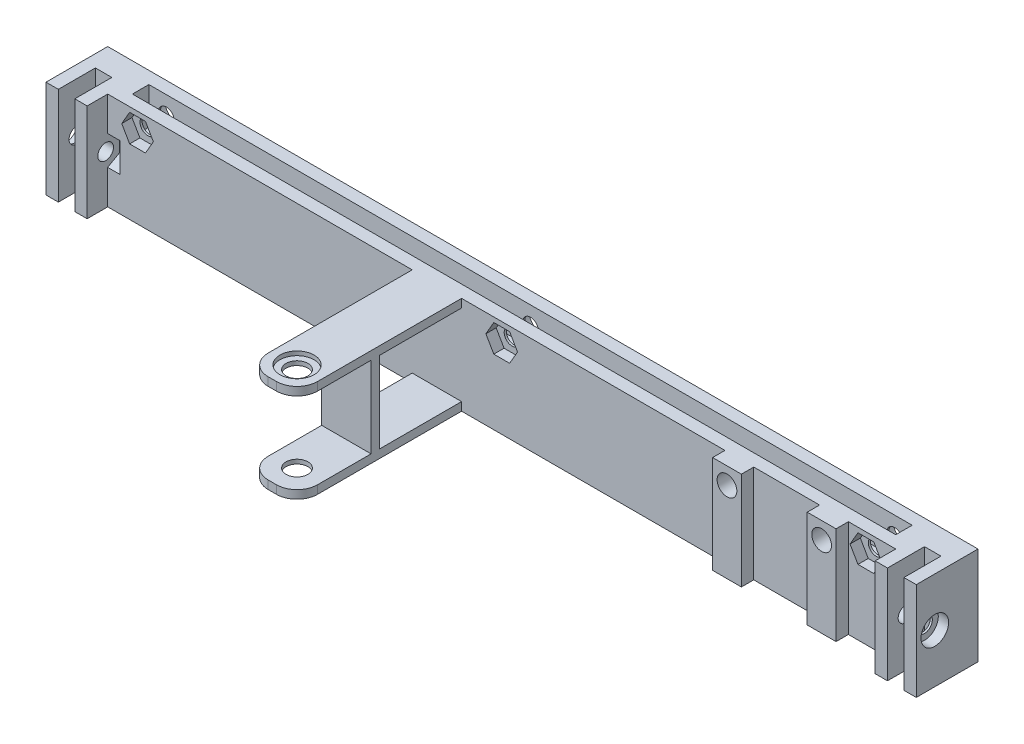
SolidWorks part; units mm, degrees
ref_plane "Front Plane" through (0, 0, 0) normal (1, 0, 0) x (0, 1, 0)
ref_plane "Top Plane" through (0, 0, 0) normal (0, 0, 1) x (0, 1, 0)
ref_plane "Right Plane" through (0, 0, 0) normal (0, 1, 0) x (-1, 0, 0)
sketch "Sketch2" plane through (0, 0, 0) normal (0, 0, 1) x (0, 1, 0)
  line L1 (-71.25, 0) -> (-95, 0)
  line L2 (-71.25, 0) -> (-71.25, 12)
  line L3 (-71.25, 12) -> (-95, 12)
  line L4 (-95, 0) -> (-95, 12)
extrude "Boss-Extrude1" add sketch "Sketch2" along normal blind 10
sketch "Sketch3" plane through (0, 0, 10) normal (0, 0, 1) x (1, 0, 0)
  line L1 (-12, -71.25) -> (0, -71.25)
  line L2 (-12, -71.25) -> (-12, -73.275)
  line L3 (-12, -73.275) -> (0, -73.275)
  line L4 (0, -71.25) -> (0, -73.275)
  line L6 (-12, -73.275) -> (0, -73.275) construction
  dimension "D1" = 2.025
extrude "Boss-Extrude2" add sketch "Sketch3" along normal blind 40
fillet "Fillet1" radius 5 2 edges at (0, -72.2625, 50) (-12, -72.2625, 50)
ref_plane "Plane1" through (0, -83.125, 0) normal (0, 1, 0) x (1, 0, 0)
mirror "Mirror1" about plane through (0, -83.125, 0) normal (0, 1, 0) of "Fillet1", "Boss-Extrude2"
sketch "Sketch5" plane through (0, -95, 0) normal (0, -1, 0) x (1, 0, 0)
  line L1 (-6, 50) -> (-12, 50)
  line L2 (-6, 50) -> (-6, 44)
  line L3 (-6, 44) -> (-12, 44)
  line L4 (-12, 50) -> (-12, 44)
  line L5 (-5, 50) -> (-7, 50) construction
  line L6 (-12, 45) -> (-12, 0) construction
  circle A0 centre (-6, 44) radius 2.65
  dimension "D1" = 6
extrude "Cut-Extrude1" cut sketch "Sketch5" against normal through all contours A0
sketch "Sketch6" plane through (0, -95, 0) normal (0, -1, 0) x (1, 0, 0)
  line L1 (-6, 50) -> (-12, 50)
  line L2 (-6, 50) -> (-6, 44)
  line L3 (-6, 44) -> (-12, 44)
  line L4 (-12, 50) -> (-12, 44)
  line L6 (-5, 50) -> (-7, 50) construction
  line L7 (-12, 45) -> (-12, 0) construction
  circle A0 centre (-6, 44) radius 4.15
  dimension "D1" = 6
extrude "Cut-Extrude2" cut sketch "Sketch6" against normal blind 1 contours A0
mirror "Mirror2" about plane through (0, -83.125, 0) normal (0, 1, 0) of "Cut-Extrude2"
sketch "Sketch7" plane through (0, 0, 0) normal (0, 0, -1) x (1, 0, 0)
  line L1 (-6, 95) -> (-96, 95)
  line L2 (-6, 95) -> (-6, 71.25)
  line L3 (-6, 71.25) -> (-96, 71.25)
  line L4 (-96, 95) -> (-96, 71.25)
  line L5 (-6, 95) -> (115.5, 95)
  line L6 (-6, 95) -> (-6, 71.25)
  line L7 (-6, 71.25) -> (115.5, 71.25)
  line L8 (115.5, 95) -> (115.5, 71.25)
  line L10 (-12, 95) -> (0, 95) construction
  line L11 (0, 71.25) -> (-12, 71.25) construction
  line M20 (0, 71.25) -> (0, 95)
  line M22 (-12, 95) -> (-12, 71.25)
  dimension "D1" = 90
  dimension "D2" = 121.5
extrude "Boss-Extrude3" add sketch "Sketch7" against normal blind 10 contours L1 L4 L3 M22 | L8 L5 L7 M20 region at (-54, -83.125, 0) region at (57.75, -83.125, 0)
sketch "Sketch8" plane through (0, 0, 10) normal (0, 0, 1) x (1, 0, 0)
  line L1 (115.5, -71.25) -> (105.5, -71.25)
  line L2 (115.5, -71.25) -> (115.5, -95)
  line L3 (115.5, -95) -> (105.5, -95)
  line L4 (105.5, -71.25) -> (105.5, -95)
  line L6 (-96, -71.25) -> (-86, -71.25)
  line L7 (-96, -71.25) -> (-96, -95)
  line L8 (-96, -95) -> (-86, -95)
  line L9 (-86, -71.25) -> (-86, -95)
  dimension "D1" = 10
  dimension "D2" = 10
extrude "Boss-Extrude4" add sketch "Sketch8" along normal blind 5
sketch "Sketch10" plane through (-12, 0, 0) normal (-1, 0, 0) x (0, -1, 0)
  line L0 (95, 45) -> (95, 10) construction
  line L1 (71.25, 10) -> (95, 10)
  line L2 (71.25, 10) -> (71.25, 12)
  line L3 (71.25, 12) -> (95, 12)
  line L4 (95, 10) -> (95, 12)
  dimension "D1" = 2
extrude "Boss-Extrude5" [suppressed] add sketch "Sketch10" along normal blind 24
sketch "Sketch18" plane through (0, -71.25, 0) normal (0, 1, 0) x (-1, 0, 0)
  line L1 (0, 10) -> (12, 10)
  line L2 (0, 10) -> (0, 30)
  line L3 (0, 30) -> (12, 30)
  line L4 (12, 10) -> (12, 30)
  line L5 (12, 45) -> (12, 10) construction
  line L6 (0, 30) -> (12, 30)
  line L7 (0, 30) -> (0, 32)
  line L8 (0, 32) -> (12, 32)
  line L9 (12, 30) -> (12, 32)
  dimension "D1" = 20
  dimension "D2" = 2
extrude "Boss-Extrude7" add sketch "Sketch18" against normal through all contours L7 L6 L9 L8
sketch "Sketch11" plane through (0, -71.25, 0) normal (0, 1, 0) x (-1, 0, 0)
  line L1 (86, 0) -> (-105.5, 0)
  line L2 (86, 0) -> (86, 10)
  line L3 (86, 10) -> (-105.5, 10)
  line L4 (-105.5, 0) -> (-105.5, 10)
  line L5 (83, 7) -> (-102.5, 7)
  line L6 (-102.5, 3) -> (-102.5, 7)
  line L7 (83, 3) -> (-102.5, 3)
  line L8 (83, 3) -> (83, 7)
  line L12 (96, 0) -> (86, 0)
  line L13 (96, 0) -> (96, 10)
  line L14 (96, 10) -> (86, 10)
  line L15 (86, 0) -> (86, 10)
extrude "Cut-Extrude3" cut sketch "Sketch11" against normal blind 9 contours L7 L8 L5 L6 region at (9.75, -71.25, 5)
mirror "Mirror3" about plane through (0, -83.125, 0) normal (0, 1, 0) of "Cut-Extrude3"
sketch "Sketch12" plane through (0, 0, 10) normal (0, 0, 1) x (1, 0, 0)
  line L1 (-86, -71.25) -> (-78.75, -71.25)
  line L2 (-86, -71.25) -> (-86, -75.75)
  line L3 (-86, -75.75) -> (-78.75, -75.75)
  line L4 (-78.75, -71.25) -> (-78.75, -75.75)
  circle A0 centre (-78.75, -75.75) radius 1.9
  circle A1 centre (-78.75, -75.75) radius 3.15
  dimension "D3" = 3.8
  dimension "D4" = 6.3
  dimension "D1" = 7.25
  dimension "D2" = 4.5
extrude "Cut-Extrude4" cut sketch "Sketch12" against normal through all and the other way through all contours A0
sketch "Sketch15" plane through (0, 0, 0) normal (0, 0, 1) x (1, 0, 0)
  circle A0 centre (-78.75, -75.75) radius 3.35
  dimension "D1" = 6.7
extrude "Cut-Extrude5" cut sketch "Sketch15" along normal blind 2.5
sketch "Sketch16" plane through (0, 0, 10) normal (0, 0, 1) x (1, 0, 0)
  line L0 (-82.5964, -75.75) -> (-80.6732, -79.0811)
  line L1 (-82.25, -75.75) -> (-80.5, -78.7811)
  line L2 (-80.5, -78.7811) -> (-77, -78.7811)
  line L3 (-77, -78.7811) -> (-75.25, -75.75)
  line L4 (-75.25, -75.75) -> (-77, -72.7189)
  line L5 (-77, -72.7189) -> (-80.5, -72.7189)
  line L6 (-80.5, -72.7189) -> (-82.25, -75.75)
  line L7 (-80.6732, -79.0811) -> (-76.8268, -79.0811)
  line L8 (-76.8268, -79.0811) -> (-74.9036, -75.75)
  line L9 (-74.9036, -75.75) -> (-76.8268, -72.4189)
  line L10 (-76.8268, -72.4189) -> (-80.6732, -72.4189)
  line L11 (-80.6732, -72.4189) -> (-82.5964, -75.75)
  line L12 (-12, -71.25) -> (-86, -71.25) construction
  circle A0 centre (-78.75, -75.75) radius 3.0311 construction
  circle M23 centre (-78.75, -75.75) radius 1.9
extrude "Cut-Extrude6" cut sketch "Sketch16" against normal blind 2.5 contours L10 L11 L0 L7 L8 L9 L6 L5 L4 L3 L2 L1 | L5 L6 L1 L2 L3 L4 M23 region at (-81.5467, -74.1353, 10) region at (-81.2948, -74.2808, 10)
pattern_linear "LPattern1" count 3 spacing 88.5 along (1, 0, 0) of "Cut-Extrude4", "Cut-Extrude6", "Cut-Extrude5"
sketch "Sketch14" plane through (0, 0, 10) normal (0, 0, 1) x (1, 0, 0)
  line L0 (0, -95) -> (105.5, -95) construction
  line L1 (105.5, -71.25) -> (94, -71.25)
  line L2 (105.5, -71.25) -> (105.5, -95)
  line L3 (105.5, -95) -> (94, -95)
  line L4 (94, -71.25) -> (94, -95)
  line L6 (94, -71.25) -> (87, -71.25)
  line L7 (94, -71.25) -> (94, -95)
  line L8 (94, -95) -> (87, -95)
  line L9 (87, -71.25) -> (87, -95)
  line L10 (87, -71.25) -> (71, -71.25)
  line L11 (87, -71.25) -> (87, -95)
  line L12 (87, -95) -> (71, -95)
  line L13 (71, -71.25) -> (71, -95)
  line L14 (71, -71.25) -> (64, -71.25)
  line L15 (71, -71.25) -> (71, -95)
  line L16 (71, -95) -> (64, -95)
  line L17 (64, -71.25) -> (64, -95)
  line M22 (105.5, -71.25) -> (0, -71.25)
  line M24 (0, -95) -> (105.5, -95)
  dimension "D1" = 11.5
  dimension "D2" = 7
  dimension "D3" = 16
  dimension "D4" = 7
extrude "Boss-Extrude6" add sketch "Sketch14" along normal blind 3 contours L17 L13 M22 M24 | L9 L4 M22 M24 region at (90.5, -83.125, 10) region at (67.5, -83.125, 10)
sketch "Sketch19" plane through (0, -83.125, 0) normal (0, 1, 0) x (1, 0, 0)
  line L1 (0, -10) -> (40, -10)
  line L2 (0, -10) -> (0, -37)
  line L3 (0, -37) -> (40, -37)
  line L4 (40, -10) -> (40, -37)
  dimension "D1" = 27
  dimension "D2" = 40
extrude "Boss-Extrude8" [suppressed] add sketch "Sketch19" against normal blind 1 and the other way blind 1
sketch "Sketch21" plane through (0, -71.25, 0) normal (0, 1, 0) x (-1, 0, 0)
  line L0 (-112.5, 6) -> (-108.5, 6)
  line L1 (-115.5, 15) -> (-112.5, 15)
  line L2 (-115.5, 15) -> (-115.5, 6)
  line L3 (-115.5, 6) -> (-112.5, 6)
  line L4 (-112.5, 15) -> (-112.5, 6)
  line L5 (-105.5, 15) -> (-108.5, 15)
  line L6 (-105.5, 15) -> (-105.5, 6)
  line L7 (-105.5, 6) -> (-108.5, 6)
  line L8 (-108.5, 15) -> (-108.5, 6)
  line M22 (-105.5, 15) -> (-115.5, 15)
  dimension "D2" = 3
  dimension "D4" = 9
extrude "Cut-Extrude7" cut sketch "Sketch21" against normal up to next contours L8 L4 L0 M22 region at (110.5, -71.25, 10.5)
pattern_linear "LPattern2" count 2 spacing 201.5 along (-1, 0, 0) of "Cut-Extrude7"
sketch "Sketch22" plane through (0, 0, 13) normal (0, 0, 1) x (1, 0, 0)
  line L1 (94, -71.25) -> (90.5, -71.25)
  line L2 (94, -71.25) -> (94, -75.37)
  line L3 (94, -75.37) -> (90.5, -75.37)
  line L4 (90.5, -71.25) -> (90.5, -75.37)
  circle A0 centre (90.5, -75.37) radius 2.4
  dimension "D1" = 4.12
extrude "Cut-Extrude8" cut sketch "Sketch22" against normal blind 3.8 contours A0
sketch "Sketch26" plane through (0, 0, 9.2) normal (0, 0, 1) x (1, 0, 0)
  circle A0 centre (90.5, -75.37) radius 1.75
extrude "Cut-Extrude12" cut sketch "Sketch26" against normal blind 0.6 contours A0
pattern_linear "LPattern3" count 2 spacing 23 along (-1, 0, 0) of "Cut-Extrude8", "Cut-Extrude12"
sketch "Sketch23" plane through (115.5, 0, 0) normal (1, 0, 0) x (0, 1, 0)
  line L0 (-95, 15) -> (-71.25, 15) construction
  line L1 (-95, 15) -> (-83.125, 15)
  line L2 (-95, 15) -> (-95, 10.5)
  line L3 (-95, 10.5) -> (-83.125, 10.5)
  line L4 (-83.125, 15) -> (-83.125, 10.5)
  circle A0 centre (-83.125, 10.5) radius 1.9
  dimension "D2" = 3.8
  dimension "D1" = 4.5
extrude "Cut-Extrude9" cut sketch "Sketch23" against normal blind 10 contours A0
sketch "Sketch24" plane through (115.5, 0, 0) normal (1, 0, 0) x (0, 1, 0)
  circle A0 centre (-83.125, 10.5) radius 3.35
  dimension "D1" = 6.7
extrude "Cut-Extrude10" cut sketch "Sketch24" against normal blind 2.5
sketch "Sketch25" plane through (105.5, 0, 0) normal (-1, 0, 0) x (0, -1, 0)
  line L0 (71.25, 15) -> (95, 15) construction
  line L1 (81.375, 13.5311) -> (79.625, 10.5)
  line L2 (79.625, 10.5) -> (81.375, 7.4689)
  line L3 (81.375, 7.4689) -> (84.875, 7.4689)
  line L4 (84.875, 7.4689) -> (86.625, 10.5)
  line L5 (86.625, 10.5) -> (84.875, 13.5311)
  line L6 (84.875, 13.5311) -> (81.375, 13.5311)
  line L7 (81.2018, 13.8311) -> (79.2786, 10.5)
  line L8 (79.2786, 10.5) -> (81.2018, 7.1689)
  line L9 (81.2018, 7.1689) -> (85.0482, 7.1689)
  line L10 (85.0482, 7.1689) -> (86.9714, 10.5)
  line L11 (86.9714, 10.5) -> (85.0482, 13.8311)
  line L12 (85.0482, 13.8311) -> (81.2018, 13.8311)
  circle A0 centre (83.125, 10.5) radius 3.0311 construction
extrude "Cut-Extrude11" cut sketch "Sketch25" along normal blind 3 contours L11 L12 L7 L8 L9 L10
ref_plane "Plane2" through (9.75, 0, 0) normal (1, 0, 0) x (0, 0, -1)
mirror "Mirror4" about plane through (9.75, 0, 0) normal (1, 0, 0) of "Cut-Extrude9", "Cut-Extrude11", "Cut-Extrude10"
equation "\"whitekey_cutout_length\"= 101.5"
equation "\"wall_thickness\"=10"
equation "\"base_mount_height\"=40"
equation "\"D1@Boss-Extrude2\"=\"base_mount_height\""
equation "\"D1@Sketch7\"=\"base_rear_length\"+\"wall_thickness\""
equation "\"D2@Sketch7\"=\"wall_thickness\"+\"base_front_length\""
equation "\"base_rear_length\"=80"
equation "\"D1@Boss-Extrude3\"=\"wall_thickness\""
equation "\"D1@Sketch8\"=\"wall_thickness\""
equation "\"D2@Sketch8\"=\"wall_thickness\""
equation "\"dowel_recess_offset\"=3"
equation "\"D1@Sketch11\"=\"dowel_recess_offset\""
equation "\"dowel_recess_depth\"=9"
equation "\"D1@Cut-Extrude3\"=\"dowel_recess_depth\""
equation "\"guide_brace_height\"=20"
equation "\"D1@Sketch18\"=\"guide_brace_height\""
equation "\"guide_brace_thickness\"=2"
equation "\"D2@Sketch18\"=\"guide_brace_thickness\""
equation "\"D3@LPattern1\"=0.5*(\"base_front_length\"+\"base_rear_length\"-\"screw_hole_wall_offset\"*2)"
equation "\"base_front_length\"=111.5"
equation "\"screw_hole_wall_offset\"=7.25"
equation "\"screw_hole_edge_inset\"=4.5"
equation "\"D1@Sketch12\"=\"screw_hole_wall_offset\""
equation "\"D2@Sketch12\"=\"screw_hole_edge_inset\""
equation "\"screw_hole_diameter\"=3.8"
equation "\"screw_head_hole_diameter\"=6.7"
equation "\"screw_nut_hole_side_len\"=3.5"
equation "\"D3@Sketch12\"=\"screw_hole_diameter\""
equation "\"D1@Sketch15\"=\"screw_head_hole_diameter\""
equation "\"D1@Sketch16\"=\"screw_nut_hole_side_len\""
equation "\"D1@Boss-Extrude6\"=6-\"dowel_recess_offset\""
equation "\"D1@Sketch21\"=\"dowel_recess_depth\""
equation "\"D2@Sketch21\"=\"dowel_recess_offset\""
equation "\"D3@Sketch21\"=\"dowel_recess_offset\""
equation "\"D4@Sketch21\"=\"dowel_recess_depth\""
equation "\"D3@LPattern2\"=\"base_front_length\"+\"base_rear_length\"+\"wall_thickness\""
equation "\"key_mount_recess_length\"=50"
equation "\"key_mount_recess_height\"=12.5"
equation "\"key_mount_recess_depth\"=1.5"
equation "\"screw_shaft_diameter\"=3.5"
equation "\"switch_board_width\"=30"
equation "\"D2@Sketch14\"=\"screw_shaft_diameter\"*2"
equation "\"D4@Sketch14\"=\"screw_shaft_diameter\"*2"
equation "\"D3@Sketch14\"=\"switch_board_width\"-\"screw_shaft_diameter\"*4"
equation "\"heatset_insert_hole_diameter\"=4.8"
equation "\"heatset_insert_hole_depth\"=3.8"
equation "\"D2@Sketch22\"=\"heatset_insert_hole_diameter\""
equation "\"D1@Cut-Extrude8\"=\"heatset_insert_hole_depth\""
equation "\"D3@LPattern3\"=\"switch_board_width\"-\"screw_shaft_diameter\"*2"
equation "\"switch_board_wall_offset\"=11.5"
equation "\"D1@Sketch14\"=\"switch_board_wall_offset\""
equation "\"D1@Sketch23\"=\"screw_hole_edge_inset\""
equation "\"D2@Sketch23\"=\"screw_hole_diameter\""
equation "\"D1@Sketch24\"=\"screw_head_hole_diameter\""
equation "\"screw_head_and_nut_recess_depth\"=2.5"
equation "\"D1@Cut-Extrude5\"=\"screw_head_and_nut_recess_depth\""
equation "\"D1@Cut-Extrude6\"=\"screw_head_and_nut_recess_depth\""
equation "\"D1@Cut-Extrude10\"=\"screw_head_and_nut_recess_depth\""
equation "\"D1@Sketch25\"=\"screw_nut_hole_side_len\""
equation "\"screw_nut_recess_offset\"=0.3"
equation "\"D2@Sketch16\"=\"screw_nut_recess_offset\""
equation "\"D2@Sketch25\"=\"screw_nut_recess_offset\""
equation "\"D1@Cut-Extrude11\"=\"screw_head_and_nut_recess_depth\"+0.5"
equation "\"D1@Cut-Extrude9\"=\"wall_thickness\""
equation "\"D1@Sketch26\"=\"screw_shaft_diameter\""
equation "\"switch_board_thickness\"=1.6"
equation "\"front_rear_panel_width\"=23.75"
equation "\"rod_length_adj\"=0.5"
equation "\"rod_insert_length\"=2.8"
equation "\"D1@Cut-Extrude12\"=6-\"heatset_insert_hole_depth\"-\"switch_board_thickness\""
